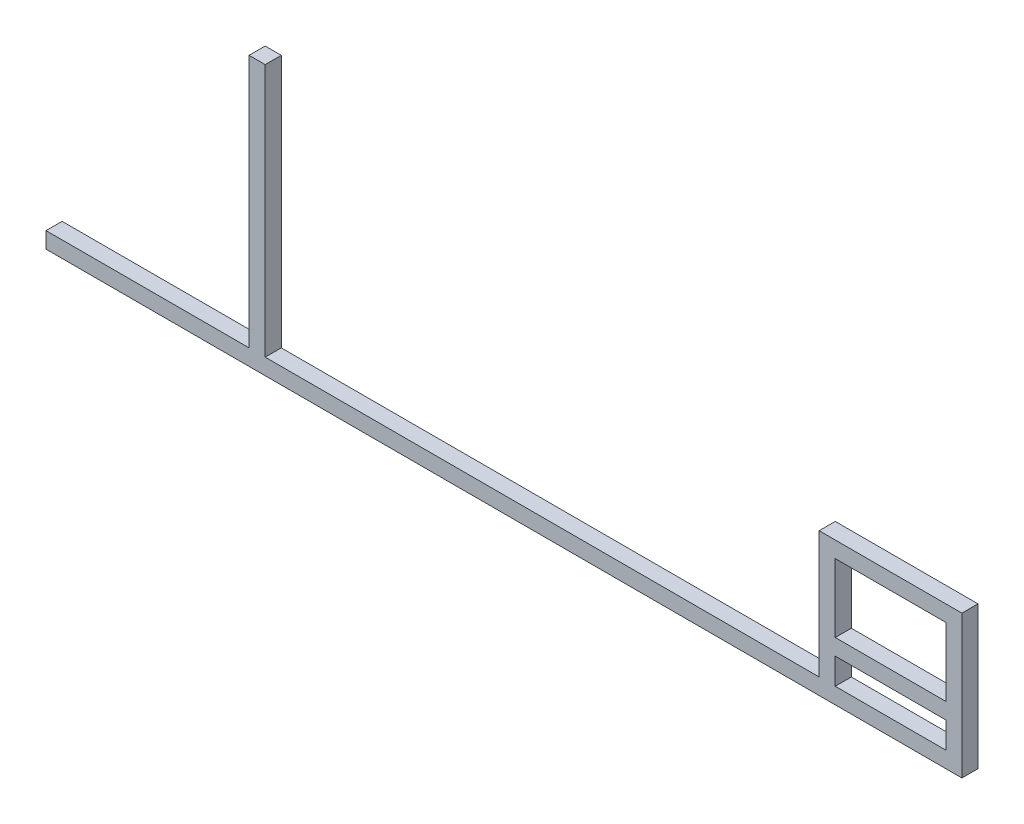
SolidWorks part; units mm, degrees
ref_plane "Front Plane" through (0, 0, 0) normal (0, 0, 1) x (1, 0, 0)
ref_plane "Top Plane" through (0, 0, 0) normal (0, 1, 0) x (1, 0, 0)
ref_plane "Right Plane" through (0, 0, 0) normal (1, 0, 0) x (0, 0, -1)
sketch "Sketch1" plane through (0, 0, 0) normal (0, 0, 1) x (1, 0, 0)
  line L0 (1869.05, 38.1) -> (1869.05, 100)
  line L1 (0, 0) -> (2169.05, 0)
  line L2 (0, 0) -> (0, 38.1)
  line L3 (0, 38.1) -> (480.95, 38.1)
  line L4 (2169.05, 0) -> (2169.05, 38.1)
  line L7 (1869.05, 338.1) -> (1830.95, 338.1)
  line L9 (1830.95, 188.1) -> (1869.05, 188.1) construction
  line L12 (1869.05, 38.1) -> (2130.95, 38.1)
  line L13 (1830.95, 38.1) -> (1830.95, 338.1)
  line L17 (2169.05, 138.1) -> (2169.05, 38.1)
  line L21 (2130.95, 138.1) -> (1869.05, 138.1)
  line L26 (2130.95, 100) -> (2130.95, 38.1)
  line L29 (2130.95, 100) -> (1869.05, 100)
  line L31 (519.05, 159.2528) -> (480.95, 159.2528) construction
  line L32 (1869.05, 138.1) -> (1869.05, 300)
  line L34 (519.05, 38.1) -> (519.05, 638.1)
  line L35 (1869.05, 338.1) -> (2169.05, 338.1)
  line L37 (1869.05, 300) -> (2130.95, 300)
  line L40 (2169.05, 138.1) -> (2169.05, 338.1)
  line L42 (2130.95, 138.1) -> (2130.95, 300)
  line L43 (519.05, 638.1) -> (480.95, 638.1)
  line L44 (2019.05, 138.1) -> (2019.05, 100) construction
  line L45 (480.95, 38.1) -> (480.95, 638.1)
  line L46 (519.05, 38.1) -> (1830.95, 38.1)
  point P5 (1850, 38.1)
  point P6 (1850, 38.1)
  point P11 (1850, 188.1)
  point P13 (2169.05, 100)
  point P14 (2169.05, 19.05)
  point P15 (2169.05, 119.05)
  point P16 (2019.05, 0)
  point P23 (500, 38.1)
  point P26 (500, 38.1)
  point P30 (1850, 338.1)
  point P31 (2019.05, 119.05)
  point P40 (500, 159.2528)
  dimension "D2" = 2169.05
  dimension "D3" = 319.05
  dimension "D5" = 300
  dimension "D7" = 138.1
  dimension "D8" = 100
  dimension "D11" = 150
  dimension "D13" = 1850
  dimension "D14" = 500
  dimension "D16" = 600
extrude "Boss-Extrude1" add sketch "Sketch1" against normal blind 38.1
shell "Shell1" thickness 3.175
